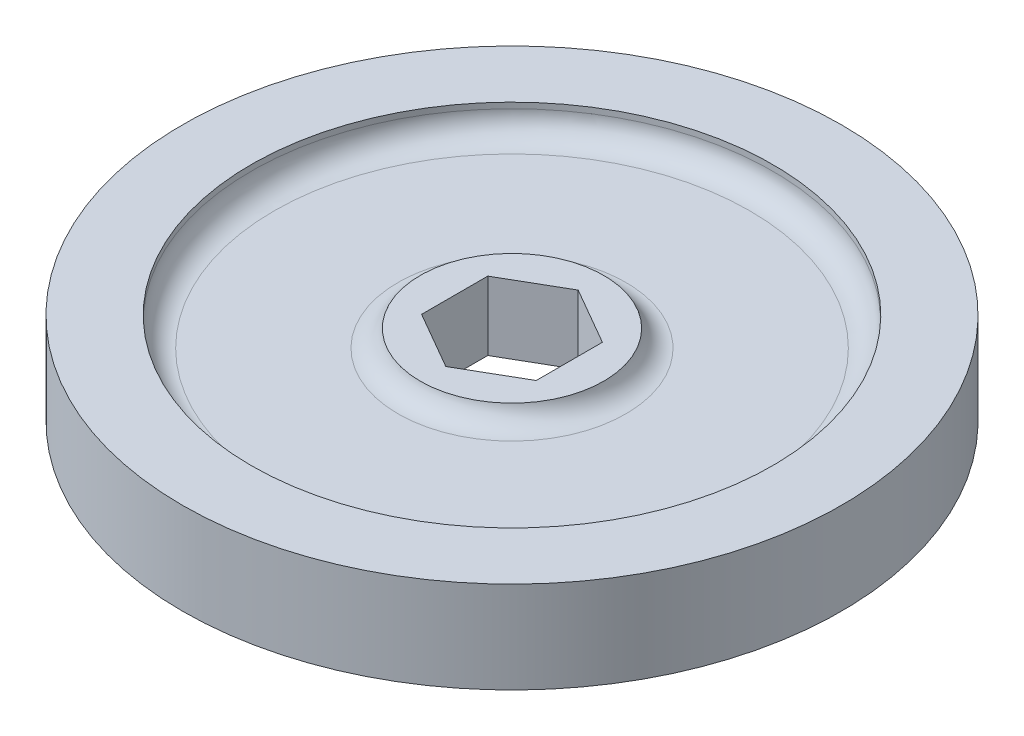
SolidWorks part; units mm, degrees
ref_plane "Front Plane" through (0, 0, 0) normal (0, 0, 1) x (1, 0, 0)
ref_plane "Top Plane" through (0, 0, 0) normal (0, 1, 0) x (1, 0, 0)
ref_plane "Right Plane" through (0, 0, 0) normal (1, 0, 0) x (0, 0, -1)
sketch "Sketch1" plane through (0, 0, 0) normal (0, 1, 0) x (1, 0, 0)
  line L1 (0, 7.3323) -> (-6.35, 3.6662)
  line L2 (-6.35, 3.6662) -> (-6.35, -3.6662)
  line L3 (-6.35, -3.6662) -> (0, -7.3323)
  line L4 (0, -7.3323) -> (6.35, -3.6662)
  line L5 (6.35, -3.6662) -> (6.35, 3.6662)
  line L6 (6.35, 3.6662) -> (0, 7.3323)
  circle A0 centre (0, 0) radius 6.35 construction
  circle A1 centre (0, 0) radius 10.16
  circle A2 centre (0, 0) radius 28.8925
  circle A3 centre (0, 0) radius 31.4325
  circle A4 centre (0, 0) radius 36.5125
  dimension "D1" = 12.7
  dimension "D2" = 20.32
  dimension "D3" = 57.785
  dimension "D4" = 62.865
  dimension "D5" = 73.025
extrude "Boss-Extrude1" add sketch "Sketch1" along normal blind 3.81 and the other way blind 3.81 contours A1 L6 L5 L4 L3 L2 L1 region at (-9.8726, 0, 0)
extrude "Boss-Extrude2" add sketch "Sketch1<3>" along normal blind 1.905 and the other way blind 1.905 contours A2 A1 region at (-28.0753, 0, 0)
sketch "Sketch1<3>" plane through (0, 0, 0) normal (0, 1, 0) x (1, 0, 0) same geometry as "Sketch1"
extrude "Boss-Extrude3" add sketch "Sketch1<4>" along normal blind 5.08 and the other way blind 5.08 contours A3 A2 region at (-30.5435, 0, 0)
sketch "Sketch1<4>" plane through (0, 0, 0) normal (0, 1, 0) x (1, 0, 0) same geometry as "Sketch1"
extrude "Boss-Extrude4" add sketch "Sketch1<5>" along normal blind 5.08 and the other way blind 5.08 contours A4 A3 region at (-35.4798, 0, 0)
sketch "Sketch1<5>" plane through (0, 0, 0) normal (0, 1, 0) x (1, 0, 0) same geometry as "Sketch1"
fillet "Fillet1" radius 2.54 4 edges at (0, -1.905, 28.8925) (0, -1.905, 10.16) (0, 1.905, 28.8925) (0, 1.905, 10.16)
